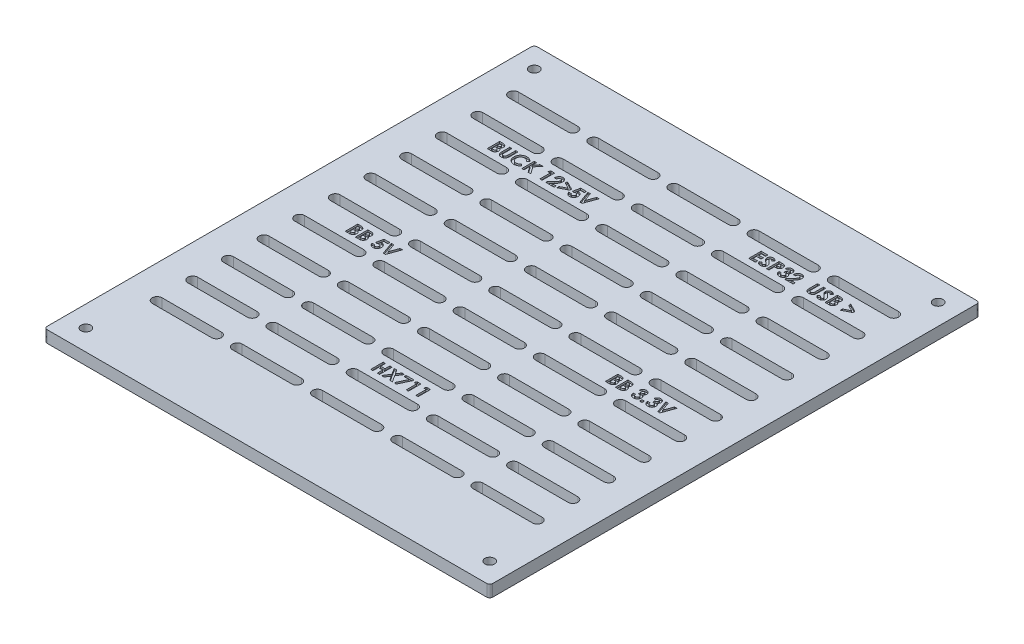
SolidWorks part; units mm, degrees
ref_plane "Front Plane" through (0, 0, 0) normal (0, 0, 1) x (1, 0, 0)
ref_plane "Top Plane" through (0, 0, 0) normal (0, 1, 0) x (1, 0, 0)
ref_plane "Right Plane" through (0, 0, 0) normal (1, 0, 0) x (0, 0, -1)
sketch "Sketch1" plane through (0, 0, 0) normal (0, 1, 0) x (1, 0, 0)
  line L0 (-74, -165) -> (74, -165)
  line L1 (75, -164) -> (75, -1)
  line L2 (74, 0) -> (-74, 0)
  line L3 (-75, -1) -> (-75, -164)
  arc A0 (-75, -164) -> (-74, -165) centre (-74, -164) ccw
  arc A1 (74, -165) -> (75, -164) centre (74, -164) ccw
  arc A2 (75, -1) -> (74, 0) centre (74, -1) ccw
  arc A3 (-74, 0) -> (-75, -1) centre (-74, -1) ccw
extrude "Floor" add sketch "Sketch1" against normal blind 4
sketch "Sketch2" plane through (0, 0, 0) normal (0, 1, 0) x (1, 0, 0)
  circle A0 centre (-68, -7) radius 1.65
  circle A1 centre (68, -7) radius 1.65
  circle A2 centre (-68, -158) radius 1.65
  circle A3 centre (68, -158) radius 1.65
extrude "Screw holes" cut sketch "Sketch2" against normal through all
sketch "Sketch3" plane through (0, 0, 0) normal (0, 1, 0) x (1, 0, 0)
  line L0 (-64, -18) -> (-44, -18) construction
  line L1 (-64, -16.35) -> (-44, -16.35)
  line L2 (-64, -19.65) -> (-44, -19.65)
  line L3 (-37, -18) -> (-17, -18) construction
  line L4 (-37, -16.35) -> (-17, -16.35)
  line L5 (-37, -19.65) -> (-17, -19.65)
  line L6 (-10, -18) -> (10, -18) construction
  line L7 (-10, -16.35) -> (10, -16.35)
  line L8 (-10, -19.65) -> (10, -19.65)
  line L9 (17, -18) -> (37, -18) construction
  line L10 (17, -16.35) -> (37, -16.35)
  line L11 (17, -19.65) -> (37, -19.65)
  line L12 (44, -18) -> (64, -18) construction
  line L13 (44, -16.35) -> (64, -16.35)
  line L14 (44, -19.65) -> (64, -19.65)
  line L15 (-64, -30) -> (-44, -30) construction
  line L16 (-64, -28.35) -> (-44, -28.35)
  line L17 (-64, -31.65) -> (-44, -31.65)
  line L18 (-37, -30) -> (-17, -30) construction
  line L19 (-37, -28.35) -> (-17, -28.35)
  line L20 (-37, -31.65) -> (-17, -31.65)
  line L21 (-10, -30) -> (10, -30) construction
  line L22 (-10, -28.35) -> (10, -28.35)
  line L23 (-10, -31.65) -> (10, -31.65)
  line L24 (17, -30) -> (37, -30) construction
  line L25 (17, -28.35) -> (37, -28.35)
  line L26 (17, -31.65) -> (37, -31.65)
  line L27 (44, -30) -> (64, -30) construction
  line L28 (44, -28.35) -> (64, -28.35)
  line L29 (44, -31.65) -> (64, -31.65)
  line L30 (-64, -42) -> (-44, -42) construction
  line L31 (-64, -40.35) -> (-44, -40.35)
  line L32 (-64, -43.65) -> (-44, -43.65)
  line L33 (-37, -42) -> (-17, -42) construction
  line L34 (-37, -40.35) -> (-17, -40.35)
  line L35 (-37, -43.65) -> (-17, -43.65)
  line L36 (-10, -42) -> (10, -42) construction
  line L37 (-10, -40.35) -> (10, -40.35)
  line L38 (-10, -43.65) -> (10, -43.65)
  line L39 (17, -42) -> (37, -42) construction
  line L40 (17, -40.35) -> (37, -40.35)
  line L41 (17, -43.65) -> (37, -43.65)
  line L42 (44, -42) -> (64, -42) construction
  line L43 (44, -40.35) -> (64, -40.35)
  line L44 (44, -43.65) -> (64, -43.65)
  line L45 (-64, -54) -> (-44, -54) construction
  line L46 (-64, -52.35) -> (-44, -52.35)
  line L47 (-64, -55.65) -> (-44, -55.65)
  line L48 (-37, -54) -> (-17, -54) construction
  line L49 (-37, -52.35) -> (-17, -52.35)
  line L50 (-37, -55.65) -> (-17, -55.65)
  line L51 (-10, -54) -> (10, -54) construction
  line L52 (-10, -52.35) -> (10, -52.35)
  line L53 (-10, -55.65) -> (10, -55.65)
  line L54 (17, -54) -> (37, -54) construction
  line L55 (17, -52.35) -> (37, -52.35)
  line L56 (17, -55.65) -> (37, -55.65)
  line L57 (44, -54) -> (64, -54) construction
  line L58 (44, -52.35) -> (64, -52.35)
  line L59 (44, -55.65) -> (64, -55.65)
  line L60 (-64, -66) -> (-44, -66) construction
  line L61 (-64, -64.35) -> (-44, -64.35)
  line L62 (-64, -67.65) -> (-44, -67.65)
  line L63 (-37, -66) -> (-17, -66) construction
  line L64 (-37, -64.35) -> (-17, -64.35)
  line L65 (-37, -67.65) -> (-17, -67.65)
  line L66 (-10, -66) -> (10, -66) construction
  line L67 (-10, -64.35) -> (10, -64.35)
  line L68 (-10, -67.65) -> (10, -67.65)
  line L69 (17, -66) -> (37, -66) construction
  line L70 (17, -64.35) -> (37, -64.35)
  line L71 (17, -67.65) -> (37, -67.65)
  line L72 (44, -66) -> (64, -66) construction
  line L73 (44, -64.35) -> (64, -64.35)
  line L74 (44, -67.65) -> (64, -67.65)
  line L75 (-64, -78) -> (-44, -78) construction
  line L76 (-64, -76.35) -> (-44, -76.35)
  line L77 (-64, -79.65) -> (-44, -79.65)
  line L78 (-37, -78) -> (-17, -78) construction
  line L79 (-37, -76.35) -> (-17, -76.35)
  line L80 (-37, -79.65) -> (-17, -79.65)
  line L81 (-10, -78) -> (10, -78) construction
  line L82 (-10, -76.35) -> (10, -76.35)
  line L83 (-10, -79.65) -> (10, -79.65)
  line L84 (17, -78) -> (37, -78) construction
  line L85 (17, -76.35) -> (37, -76.35)
  line L86 (17, -79.65) -> (37, -79.65)
  line L87 (44, -78) -> (64, -78) construction
  line L88 (44, -76.35) -> (64, -76.35)
  line L89 (44, -79.65) -> (64, -79.65)
  line L90 (-64, -90) -> (-44, -90) construction
  line L91 (-64, -88.35) -> (-44, -88.35)
  line L92 (-64, -91.65) -> (-44, -91.65)
  line L93 (-37, -90) -> (-17, -90) construction
  line L94 (-37, -88.35) -> (-17, -88.35)
  line L95 (-37, -91.65) -> (-17, -91.65)
  line L96 (-10, -90) -> (10, -90) construction
  line L97 (-10, -88.35) -> (10, -88.35)
  line L98 (-10, -91.65) -> (10, -91.65)
  line L99 (17, -90) -> (37, -90) construction
  line L100 (17, -88.35) -> (37, -88.35)
  line L101 (17, -91.65) -> (37, -91.65)
  line L102 (44, -90) -> (64, -90) construction
  line L103 (44, -88.35) -> (64, -88.35)
  line L104 (44, -91.65) -> (64, -91.65)
  line L105 (-64, -102) -> (-44, -102) construction
  line L106 (-64, -100.35) -> (-44, -100.35)
  line L107 (-64, -103.65) -> (-44, -103.65)
  line L108 (-37, -102) -> (-17, -102) construction
  line L109 (-37, -100.35) -> (-17, -100.35)
  line L110 (-37, -103.65) -> (-17, -103.65)
  line L111 (-10, -102) -> (10, -102) construction
  line L112 (-10, -100.35) -> (10, -100.35)
  line L113 (-10, -103.65) -> (10, -103.65)
  line L114 (17, -102) -> (37, -102) construction
  line L115 (17, -100.35) -> (37, -100.35)
  line L116 (17, -103.65) -> (37, -103.65)
  line L117 (44, -102) -> (64, -102) construction
  line L118 (44, -100.35) -> (64, -100.35)
  line L119 (44, -103.65) -> (64, -103.65)
  line L120 (-64, -114) -> (-44, -114) construction
  line L121 (-64, -112.35) -> (-44, -112.35)
  line L122 (-64, -115.65) -> (-44, -115.65)
  line L123 (-37, -114) -> (-17, -114) construction
  line L124 (-37, -112.35) -> (-17, -112.35)
  line L125 (-37, -115.65) -> (-17, -115.65)
  line L126 (-10, -114) -> (10, -114) construction
  line L127 (-10, -112.35) -> (10, -112.35)
  line L128 (-10, -115.65) -> (10, -115.65)
  line L129 (17, -114) -> (37, -114) construction
  line L130 (17, -112.35) -> (37, -112.35)
  line L131 (17, -115.65) -> (37, -115.65)
  line L132 (44, -114) -> (64, -114) construction
  line L133 (44, -112.35) -> (64, -112.35)
  line L134 (44, -115.65) -> (64, -115.65)
  line L135 (-64, -126) -> (-44, -126) construction
  line L136 (-64, -124.35) -> (-44, -124.35)
  line L137 (-64, -127.65) -> (-44, -127.65)
  line L138 (-37, -126) -> (-17, -126) construction
  line L139 (-37, -124.35) -> (-17, -124.35)
  line L140 (-37, -127.65) -> (-17, -127.65)
  line L141 (-10, -126) -> (10, -126) construction
  line L142 (-10, -124.35) -> (10, -124.35)
  line L143 (-10, -127.65) -> (10, -127.65)
  line L144 (17, -126) -> (37, -126) construction
  line L145 (17, -124.35) -> (37, -124.35)
  line L146 (17, -127.65) -> (37, -127.65)
  line L147 (44, -126) -> (64, -126) construction
  line L148 (44, -124.35) -> (64, -124.35)
  line L149 (44, -127.65) -> (64, -127.65)
  line L150 (-64, -138) -> (-44, -138) construction
  line L151 (-64, -136.35) -> (-44, -136.35)
  line L152 (-64, -139.65) -> (-44, -139.65)
  line L153 (-37, -138) -> (-17, -138) construction
  line L154 (-37, -136.35) -> (-17, -136.35)
  line L155 (-37, -139.65) -> (-17, -139.65)
  line L156 (-10, -138) -> (10, -138) construction
  line L157 (-10, -136.35) -> (10, -136.35)
  line L158 (-10, -139.65) -> (10, -139.65)
  line L159 (17, -138) -> (37, -138) construction
  line L160 (17, -136.35) -> (37, -136.35)
  line L161 (17, -139.65) -> (37, -139.65)
  line L162 (44, -138) -> (64, -138) construction
  line L163 (44, -136.35) -> (64, -136.35)
  line L164 (44, -139.65) -> (64, -139.65)
  arc A0 (-64, -16.35) -> (-64, -19.65) centre (-64, -18) ccw
  arc A1 (-44, -19.65) -> (-44, -16.35) centre (-44, -18) ccw
  arc A2 (-37, -16.35) -> (-37, -19.65) centre (-37, -18) ccw
  arc A3 (-17, -19.65) -> (-17, -16.35) centre (-17, -18) ccw
  arc A4 (-10, -16.35) -> (-10, -19.65) centre (-10, -18) ccw
  arc A5 (10, -19.65) -> (10, -16.35) centre (10, -18) ccw
  arc A6 (17, -16.35) -> (17, -19.65) centre (17, -18) ccw
  arc A7 (37, -19.65) -> (37, -16.35) centre (37, -18) ccw
  arc A8 (44, -16.35) -> (44, -19.65) centre (44, -18) ccw
  arc A9 (64, -19.65) -> (64, -16.35) centre (64, -18) ccw
  arc A10 (-64, -28.35) -> (-64, -31.65) centre (-64, -30) ccw
  arc A11 (-44, -31.65) -> (-44, -28.35) centre (-44, -30) ccw
  arc A12 (-37, -28.35) -> (-37, -31.65) centre (-37, -30) ccw
  arc A13 (-17, -31.65) -> (-17, -28.35) centre (-17, -30) ccw
  arc A14 (-10, -28.35) -> (-10, -31.65) centre (-10, -30) ccw
  arc A15 (10, -31.65) -> (10, -28.35) centre (10, -30) ccw
  arc A16 (17, -28.35) -> (17, -31.65) centre (17, -30) ccw
  arc A17 (37, -31.65) -> (37, -28.35) centre (37, -30) ccw
  arc A18 (44, -28.35) -> (44, -31.65) centre (44, -30) ccw
  arc A19 (64, -31.65) -> (64, -28.35) centre (64, -30) ccw
  arc A20 (-64, -40.35) -> (-64, -43.65) centre (-64, -42) ccw
  arc A21 (-44, -43.65) -> (-44, -40.35) centre (-44, -42) ccw
  arc A22 (-37, -40.35) -> (-37, -43.65) centre (-37, -42) ccw
  arc A23 (-17, -43.65) -> (-17, -40.35) centre (-17, -42) ccw
  arc A24 (-10, -40.35) -> (-10, -43.65) centre (-10, -42) ccw
  arc A25 (10, -43.65) -> (10, -40.35) centre (10, -42) ccw
  arc A26 (17, -40.35) -> (17, -43.65) centre (17, -42) ccw
  arc A27 (37, -43.65) -> (37, -40.35) centre (37, -42) ccw
  arc A28 (44, -40.35) -> (44, -43.65) centre (44, -42) ccw
  arc A29 (64, -43.65) -> (64, -40.35) centre (64, -42) ccw
  arc A30 (-64, -52.35) -> (-64, -55.65) centre (-64, -54) ccw
  arc A31 (-44, -55.65) -> (-44, -52.35) centre (-44, -54) ccw
  arc A32 (-37, -52.35) -> (-37, -55.65) centre (-37, -54) ccw
  arc A33 (-17, -55.65) -> (-17, -52.35) centre (-17, -54) ccw
  arc A34 (-10, -52.35) -> (-10, -55.65) centre (-10, -54) ccw
  arc A35 (10, -55.65) -> (10, -52.35) centre (10, -54) ccw
  arc A36 (17, -52.35) -> (17, -55.65) centre (17, -54) ccw
  arc A37 (37, -55.65) -> (37, -52.35) centre (37, -54) ccw
  arc A38 (44, -52.35) -> (44, -55.65) centre (44, -54) ccw
  arc A39 (64, -55.65) -> (64, -52.35) centre (64, -54) ccw
  arc A40 (-64, -64.35) -> (-64, -67.65) centre (-64, -66) ccw
  arc A41 (-44, -67.65) -> (-44, -64.35) centre (-44, -66) ccw
  arc A42 (-37, -64.35) -> (-37, -67.65) centre (-37, -66) ccw
  arc A43 (-17, -67.65) -> (-17, -64.35) centre (-17, -66) ccw
  arc A44 (-10, -64.35) -> (-10, -67.65) centre (-10, -66) ccw
  arc A45 (10, -67.65) -> (10, -64.35) centre (10, -66) ccw
  arc A46 (17, -64.35) -> (17, -67.65) centre (17, -66) ccw
  arc A47 (37, -67.65) -> (37, -64.35) centre (37, -66) ccw
  arc A48 (44, -64.35) -> (44, -67.65) centre (44, -66) ccw
  arc A49 (64, -67.65) -> (64, -64.35) centre (64, -66) ccw
  arc A50 (-64, -76.35) -> (-64, -79.65) centre (-64, -78) ccw
  arc A51 (-44, -79.65) -> (-44, -76.35) centre (-44, -78) ccw
  arc A52 (-37, -76.35) -> (-37, -79.65) centre (-37, -78) ccw
  arc A53 (-17, -79.65) -> (-17, -76.35) centre (-17, -78) ccw
  arc A54 (-10, -76.35) -> (-10, -79.65) centre (-10, -78) ccw
  arc A55 (10, -79.65) -> (10, -76.35) centre (10, -78) ccw
  arc A56 (17, -76.35) -> (17, -79.65) centre (17, -78) ccw
  arc A57 (37, -79.65) -> (37, -76.35) centre (37, -78) ccw
  arc A58 (44, -76.35) -> (44, -79.65) centre (44, -78) ccw
  arc A59 (64, -79.65) -> (64, -76.35) centre (64, -78) ccw
  arc A60 (-64, -88.35) -> (-64, -91.65) centre (-64, -90) ccw
  arc A61 (-44, -91.65) -> (-44, -88.35) centre (-44, -90) ccw
  arc A62 (-37, -88.35) -> (-37, -91.65) centre (-37, -90) ccw
  arc A63 (-17, -91.65) -> (-17, -88.35) centre (-17, -90) ccw
  arc A64 (-10, -88.35) -> (-10, -91.65) centre (-10, -90) ccw
  arc A65 (10, -91.65) -> (10, -88.35) centre (10, -90) ccw
  arc A66 (17, -88.35) -> (17, -91.65) centre (17, -90) ccw
  arc A67 (37, -91.65) -> (37, -88.35) centre (37, -90) ccw
  arc A68 (44, -88.35) -> (44, -91.65) centre (44, -90) ccw
  arc A69 (64, -91.65) -> (64, -88.35) centre (64, -90) ccw
  arc A70 (-64, -100.35) -> (-64, -103.65) centre (-64, -102) ccw
  arc A71 (-44, -103.65) -> (-44, -100.35) centre (-44, -102) ccw
  arc A72 (-37, -100.35) -> (-37, -103.65) centre (-37, -102) ccw
  arc A73 (-17, -103.65) -> (-17, -100.35) centre (-17, -102) ccw
  arc A74 (-10, -100.35) -> (-10, -103.65) centre (-10, -102) ccw
  arc A75 (10, -103.65) -> (10, -100.35) centre (10, -102) ccw
  arc A76 (17, -100.35) -> (17, -103.65) centre (17, -102) ccw
  arc A77 (37, -103.65) -> (37, -100.35) centre (37, -102) ccw
  arc A78 (44, -100.35) -> (44, -103.65) centre (44, -102) ccw
  arc A79 (64, -103.65) -> (64, -100.35) centre (64, -102) ccw
  arc A80 (-64, -112.35) -> (-64, -115.65) centre (-64, -114) ccw
  arc A81 (-44, -115.65) -> (-44, -112.35) centre (-44, -114) ccw
  arc A82 (-37, -112.35) -> (-37, -115.65) centre (-37, -114) ccw
  arc A83 (-17, -115.65) -> (-17, -112.35) centre (-17, -114) ccw
  arc A84 (-10, -112.35) -> (-10, -115.65) centre (-10, -114) ccw
  arc A85 (10, -115.65) -> (10, -112.35) centre (10, -114) ccw
  arc A86 (17, -112.35) -> (17, -115.65) centre (17, -114) ccw
  arc A87 (37, -115.65) -> (37, -112.35) centre (37, -114) ccw
  arc A88 (44, -112.35) -> (44, -115.65) centre (44, -114) ccw
  arc A89 (64, -115.65) -> (64, -112.35) centre (64, -114) ccw
  arc A90 (-64, -124.35) -> (-64, -127.65) centre (-64, -126) ccw
  arc A91 (-44, -127.65) -> (-44, -124.35) centre (-44, -126) ccw
  arc A92 (-37, -124.35) -> (-37, -127.65) centre (-37, -126) ccw
  arc A93 (-17, -127.65) -> (-17, -124.35) centre (-17, -126) ccw
  arc A94 (-10, -124.35) -> (-10, -127.65) centre (-10, -126) ccw
  arc A95 (10, -127.65) -> (10, -124.35) centre (10, -126) ccw
  arc A96 (17, -124.35) -> (17, -127.65) centre (17, -126) ccw
  arc A97 (37, -127.65) -> (37, -124.35) centre (37, -126) ccw
  arc A98 (44, -124.35) -> (44, -127.65) centre (44, -126) ccw
  arc A99 (64, -127.65) -> (64, -124.35) centre (64, -126) ccw
  arc A100 (-64, -136.35) -> (-64, -139.65) centre (-64, -138) ccw
  arc A101 (-44, -139.65) -> (-44, -136.35) centre (-44, -138) ccw
  arc A102 (-37, -136.35) -> (-37, -139.65) centre (-37, -138) ccw
  arc A103 (-17, -139.65) -> (-17, -136.35) centre (-17, -138) ccw
  arc A104 (-10, -136.35) -> (-10, -139.65) centre (-10, -138) ccw
  arc A105 (10, -139.65) -> (10, -136.35) centre (10, -138) ccw
  arc A106 (17, -136.35) -> (17, -139.65) centre (17, -138) ccw
  arc A107 (37, -139.65) -> (37, -136.35) centre (37, -138) ccw
  arc A108 (44, -136.35) -> (44, -139.65) centre (44, -138) ccw
  arc A109 (64, -139.65) -> (64, -136.35) centre (64, -138) ccw
  point P2 (-54, -18)
  point P7 (-27, -18)
  point P14 (0, -18)
  point P21 (27, -18)
  point P28 (54, -18)
  point P35 (-54, -30)
  point P42 (-27, -30)
  point P49 (0, -30)
  point P56 (27, -30)
  point P63 (54, -30)
  point P70 (-54, -42)
  point P77 (-27, -42)
  point P84 (0, -42)
  point P91 (27, -42)
  point P98 (54, -42)
  point P105 (-54, -54)
  point P112 (-27, -54)
  point P119 (0, -54)
  point P126 (27, -54)
  point P133 (54, -54)
  point P140 (-54, -66)
  point P147 (-27, -66)
  point P154 (0, -66)
  point P161 (27, -66)
  point P168 (54, -66)
  point P175 (-54, -78)
  point P182 (-27, -78)
  point P189 (0, -78)
  point P196 (27, -78)
  point P203 (54, -78)
  point P210 (-54, -90)
  point P217 (-27, -90)
  point P224 (0, -90)
  point P231 (27, -90)
  point P238 (54, -90)
  point P245 (-54, -102)
  point P252 (-27, -102)
  point P259 (0, -102)
  point P266 (27, -102)
  point P273 (54, -102)
  point P280 (-54, -114)
  point P287 (-27, -114)
  point P294 (0, -114)
  point P301 (27, -114)
  point P308 (54, -114)
  point P315 (-54, -126)
  point P322 (-27, -126)
  point P329 (0, -126)
  point P336 (27, -126)
  point P343 (54, -126)
  point P350 (-54, -138)
  point P357 (-27, -138)
  point P364 (0, -138)
  point P371 (27, -138)
  point P378 (54, -138)
  point P385 (0, 0)
extrude "Mounting slots" cut sketch "Sketch3" against normal through all
sketch "Sketch4" plane through (0, 0, 0) normal (0, 1, 0) x (1, 0, 0)
  text T0 "BUCK 12>5V" font "Century Gothic" height 4.2
  text T1 "ESP32  USB >" font "Century Gothic" height 4.2
  text T2 "BB 5V" font "Century Gothic" height 4.2
  text T3 "BB 3.3V" font "Century Gothic" height 4.2
  text T4 "HX711" font "Century Gothic" height 4.2
extrude "Zone labels" cut sketch "Sketch4" against normal blind 0.6
ref_plane "P1_Top_-4" through (0, -4, 0) normal (0, 1, 0) x (1, 0, 0)
sketch "Sketch5" plane through (0, -4, 0) normal (0, 1, 0) x (1, 0, 0)
  circle A0 centre (-60, -15) radius 5
  circle A1 centre (-60, -150) radius 5
  circle A2 centre (60, -15) radius 5
  circle A3 centre (60, -150) radius 5
extrude "Feet" add sketch "Sketch5" against normal blind 3
